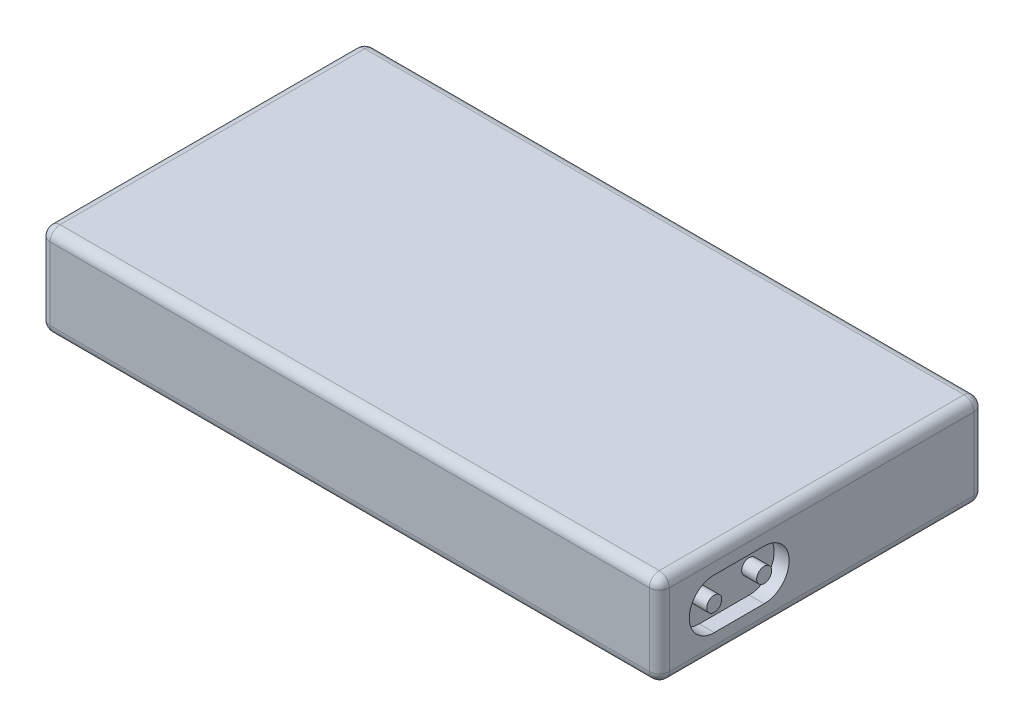
SolidWorks part; units mm, degrees
material "Резина"
ref_plane "Спереди" through (0, 0, 0) normal (0, 0, 1) x (1, 0, 0)
ref_plane "Сверху" through (0, 0, 0) normal (0, 1, 0) x (1, 0, 0)
ref_plane "Справа" through (0, 0, 0) normal (1, 0, 0) x (0, 0, -1)
sketch "Эскиз1" plane through (0, 0, 0) normal (0, 1, 0) x (1, 0, 0)
  line L0 (0, 0) -> (124, 0)
  line L1 (0, 0) -> (0, 65)
  line L2 (124, 0) -> (124, 65)
  line L3 (0, 65) -> (124, 65)
  dimension "D1" = 124
  dimension "D2" = 65
extrude "Бобышка-Вытянуть1" add sketch "Эскиз1" along normal blind 18.5
sketch "Эскиз2" plane through (124, 0, 0) normal (1, 0, 0) x (0, 0, -1)
  line L0 (0, 9.25) -> (65, 9.25) construction
  line L1 (0, 18.5) -> (0, 0) construction
  line L2 (65, 18.5) -> (65, 0) construction
  line L3 (5, 15.25) -> (5, 3.25) construction
  line L4 (5, 15.25) -> (27, 15.25) construction
  line L5 (5, 3.25) -> (27, 3.25) construction
  line L6 (27, 15.25) -> (27, 3.25) construction
  line L7 (11, 9.25) -> (21, 9.25) construction
  line L8 (11, 14.25) -> (21, 14.25)
  line L9 (11, 4.25) -> (21, 4.25)
  line L10 (16, 15.25) -> (16, 3.25) construction
  arc A0 (11, 14.25) -> (11, 4.25) centre (11, 9.25) ccw
  arc A1 (21, 4.25) -> (21, 14.25) centre (21, 9.25) ccw
  circle A2 centre (11, 9.25) radius 1.5
  circle A3 centre (21, 9.25) radius 1.5
  point P6 (27, 9.25)
  point P11 (16, 9.25)
  dimension "D5" = 5
  dimension "D6" = 3
  dimension "D1" = 5
  dimension "D2" = 22
  dimension "D3" = 12
  dimension "D4" = 10
extrude "Вырез-Вытянуть1" cut sketch "Эскиз2" against normal blind 3
sketch "Эскиз3" plane through (0, 0, 0) normal (-1, 0, 0) x (0, 0, 1)
  line L0 (-65, 9.25) -> (0, 9.25) construction
  line L1 (-65, 18.5) -> (-65, 0) construction
  line L2 (0, 18.5) -> (0, 0) construction
  line L3 (-59, 12.75) -> (-59, 5.75)
  line L4 (-59, 12.75) -> (-45, 12.75)
  line L5 (-59, 5.75) -> (-45, 5.75)
  line L6 (-45, 12.75) -> (-45, 5.75)
  line L7 (-58, 8.75) -> (-58, 6.75)
  line L8 (-58, 8.75) -> (-46, 8.75)
  line L9 (-58, 6.75) -> (-46, 6.75)
  line L10 (-46, 8.75) -> (-46, 6.75)
  point P6 (-59, 9.25)
  dimension "D1" = 14
  dimension "D2" = 6
  dimension "D3" = 7
  dimension "D4" = 2
  dimension "D5" = 1
  dimension "D6" = 1
  dimension "D7" = 1
extrude "Вырез-Вытянуть2" cut sketch "Эскиз3" against normal blind 3
sketch "Эскиз4" plane through (0, 0, 0) normal (-1, 0, 0) x (0, 0, 1)
  line L0 (-65, 9.25) -> (0, 9.25) construction
  line L1 (-65, 18.5) -> (-65, 0) construction
  line L2 (0, 18.5) -> (0, 0) construction
  line L3 (-20, 12.75) -> (-20, 5.75) construction
  line L4 (-20, 12.75) -> (-6, 12.75) construction
  line L5 (-20, 5.75) -> (-6, 5.75) construction
  line L6 (-6, 12.75) -> (-6, 5.75) construction
  line L7 (-19, 9.25) -> (-16, 12.25)
  line L8 (-16, 12.25) -> (-10, 12.25)
  line L9 (-10, 12.25) -> (-7, 9.25)
  line L10 (-10, 6.25) -> (-7, 9.25)
  line L11 (-16, 6.25) -> (-10, 6.25)
  line L12 (-19, 9.25) -> (-16, 6.25)
  line L13 (-13, 12.25) -> (-13, 6.25) construction
  line L14 (-16, 12.25) -> (-16, 6.25) construction
  line L15 (-10, 12.25) -> (-10, 6.25) construction
  line L16 (-14, 9.25) -> (-12, 9.25) construction
  line L17 (-13, 12.75) -> (-13, 5.75) construction
  circle A0 centre (-16, 9.25) radius 0.5
  circle A1 centre (-14, 9.25) radius 0.5
  circle A2 centre (-12, 9.25) radius 0.5
  circle A3 centre (-10, 9.25) radius 0.5
  point P6 (-20, 9.25)
  point P27 (-13, 9.25)
  dimension "D8" = 2
  dimension "D9" = 2
  dimension "D10" = 2
  dimension "D11" = 1
  dimension "D1" = 14
  dimension "D2" = 6
  dimension "D3" = 7
  dimension "D4" = 45
  dimension "D6" = 6
  dimension "D7" = 6
extrude "Вырез-Вытянуть3" cut sketch "Эскиз4" against normal blind 3
fillet "Скругление1" radius 2 4 edges at (124, 18.5, -32.5) (62, 18.5, -65) (0, 18.5, -32.5) (62, 18.5, 0)
fillet "Скругление2" radius 2 4 edges at (62, 0, 0) (124, 0, -32.5) (62, 0, -65) (0, 0, -32.5)
fillet "Скругление3" radius 2 6 edges at (123.4142, 17.9142, -0.5858) (123.4142, 0.5858, -0.5858) (0.5858, 17.9142, -0.5858) (0.5858, 0.5858, -0.5858) (124, 9.25, 0) (0, 9.25, 0)
fillet "Скругление4" radius 2 6 edges at (0.5858, 17.9142, -64.4142) (0.5858, 0.5858, -64.4142) (123.4142, 17.9142, -64.4142) (123.4142, 0.5858, -64.4142) (0, 9.25, -65) (124, 9.25, -65)
sketch "Эскиз5" plane through (0, 0, -65) normal (0, 0, -1) x (-1, 0, 0)
  line L0 (-2, 9.25) -> (-122, 9.25) construction
  line L1 (-2, 2) -> (-2, 16.5) construction
  line L2 (-122, 16.5) -> (-122, 2) construction
ref_plane "Блок питания Симм" through (0, 9.25, 0) normal (0, 1, 0) x (1, 0, 0)
